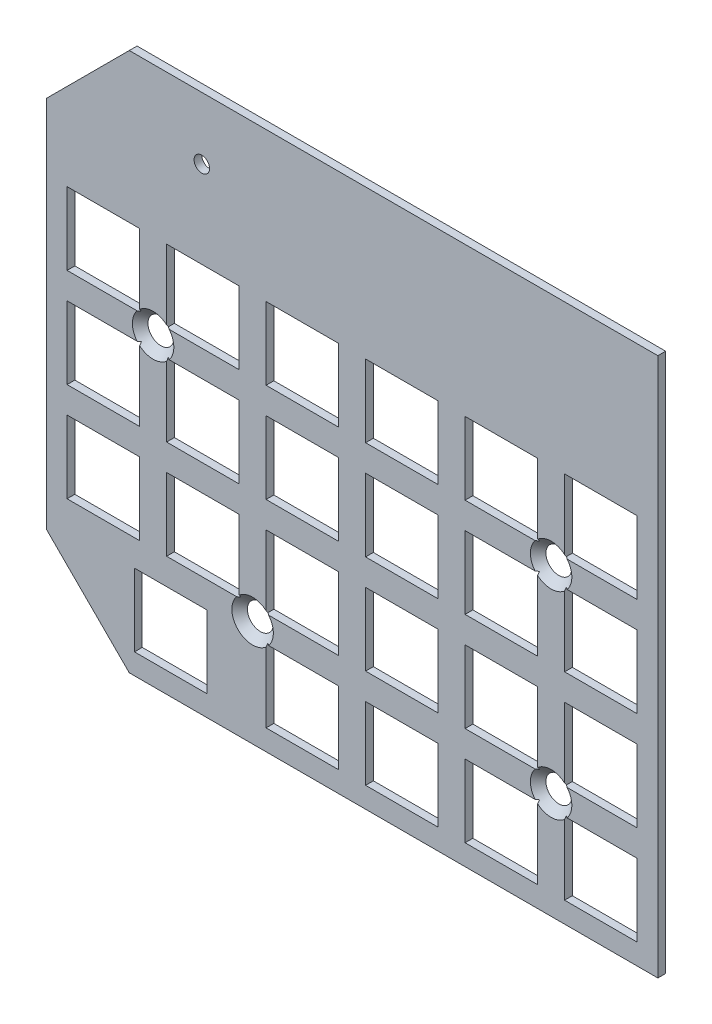
SolidWorks part; units mm, degrees
material "Alliage 1060"
ref_plane "Plan de face" through (0, 0, 0) normal (0, 0, 1) x (1, 0, 0)
ref_plane "Plan de dessus" through (0, 0, 0) normal (0, 1, 0) x (1, 0, 0)
ref_plane "Plan de droite" through (0, 0, 0) normal (1, 0, 0) x (0, 0, -1)
other "Centre de masse"
sketch "Esquisse1" plane through (0, 0, 0) normal (0, 0, 1) x (1, 0, 0)
  line L0 (0, -85) -> (16, -101)
  line L4 (118, 3) -> (118, -101)
  line L5 (16, 3) -> (0, -13)
  line L7 (118, 3) -> (16, 3)
  line L8 (0, -13) -> (0, -85)
  line L9 (16, -101) -> (118, -101)
  dimension "D1" = 104
  dimension "D2" = 118
  dimension "D3" = 16
  dimension "D4" = 16
  dimension "D5" = 16
  dimension "D6" = 16
extrude "Boss.-Extru.1" add sketch "Esquisse1" along normal blind 1.5
sketch "Esquisse2" plane through (0, 0, 1.5) normal (0, 0, 1) x (1, 0, 0)
  line L0 (0, -13) -> (0, -85) construction
  line L1 (4, -25.7494) -> (18, -25.7494)
  line L2 (4, -25.7494) -> (4, -39.7494)
  line L3 (4, -39.7494) -> (18, -39.7494)
  line L4 (18, -25.7494) -> (18, -39.7494)
  line L5 (11, -39.7494) -> (11, -25.7494) construction
  line L6 (4, -32.7494) -> (18, -32.7494) construction
  line L7 (118, 3) -> (16, 3) construction
  line L12 (23.2, -25.7494) -> (23.2, -39.7494)
  line L13 (23.2, -25.7494) -> (37.2, -25.7494)
  line L14 (37.2, -25.7494) -> (37.2, -39.7494)
  line L15 (23.2, -39.7494) -> (37.2, -39.7494)
  line L16 (42.4, -25.7494) -> (42.4, -39.7494)
  line L17 (42.4, -25.7494) -> (56.4, -25.7494)
  line L18 (56.4, -25.7494) -> (56.4, -39.7494)
  line L19 (42.4, -39.7494) -> (56.4, -39.7494)
  line L20 (61.6, -25.7494) -> (61.6, -39.7494)
  line L21 (61.6, -25.7494) -> (75.6, -25.7494)
  line L22 (75.6, -25.7494) -> (75.6, -39.7494)
  line L23 (61.6, -39.7494) -> (75.6, -39.7494)
  line L24 (80.8, -25.7494) -> (80.8, -39.7494)
  line L25 (80.8, -25.7494) -> (94.8, -25.7494)
  line L26 (94.8, -25.7494) -> (94.8, -39.7494)
  line L27 (80.8, -39.7494) -> (94.8, -39.7494)
  line L28 (100, -25.7494) -> (100, -39.7494)
  line L29 (100, -25.7494) -> (114, -25.7494)
  line L30 (114, -25.7494) -> (114, -39.7494)
  line L31 (100, -39.7494) -> (114, -39.7494)
  line L32 (23.2, -44.8329) -> (23.2, -58.8329)
  line L33 (23.2, -44.8329) -> (37.2, -44.8329)
  line L34 (37.2, -44.8329) -> (37.2, -58.8329)
  line L35 (23.2, -58.8329) -> (37.2, -58.8329)
  line L36 (42.4, -44.8329) -> (42.4, -58.8329)
  line L37 (42.4, -44.8329) -> (56.4, -44.8329)
  line L38 (56.4, -44.8329) -> (56.4, -58.8329)
  line L39 (42.4, -58.8329) -> (56.4, -58.8329)
  line L40 (61.6, -44.8329) -> (61.6, -58.8329)
  line L41 (61.6, -44.8329) -> (75.6, -44.8329)
  line L42 (75.6, -44.8329) -> (75.6, -58.8329)
  line L43 (61.6, -58.8329) -> (75.6, -58.8329)
  line L44 (80.8, -44.8329) -> (80.8, -58.8329)
  line L45 (80.8, -44.8329) -> (94.8, -44.8329)
  line L46 (94.8, -44.8329) -> (94.8, -58.8329)
  line L47 (80.8, -58.8329) -> (94.8, -58.8329)
  line L48 (100, -44.8329) -> (100, -58.8329)
  line L49 (100, -44.8329) -> (114, -44.8329)
  line L50 (114, -44.8329) -> (114, -58.8329)
  line L51 (100, -58.8329) -> (114, -58.8329)
  line L52 (23.2, -63.9165) -> (23.2, -77.9165)
  line L53 (23.2, -63.9165) -> (37.2, -63.9165)
  line L54 (37.2, -63.9165) -> (37.2, -77.9165)
  line L55 (23.2, -77.9165) -> (37.2, -77.9165)
  line L56 (42.4, -63.9165) -> (42.4, -77.9165)
  line L57 (42.4, -63.9165) -> (56.4, -63.9165)
  line L58 (56.4, -63.9165) -> (56.4, -77.9165)
  line L59 (42.4, -77.9165) -> (56.4, -77.9165)
  line L60 (61.6, -63.9165) -> (61.6, -77.9165)
  line L61 (61.6, -63.9165) -> (75.6, -63.9165)
  line L62 (75.6, -63.9165) -> (75.6, -77.9165)
  line L63 (61.6, -77.9165) -> (75.6, -77.9165)
  line L64 (80.8, -63.9165) -> (80.8, -77.9165)
  line L65 (80.8, -63.9165) -> (94.8, -63.9165)
  line L66 (94.8, -63.9165) -> (94.8, -77.9165)
  line L67 (80.8, -77.9165) -> (94.8, -77.9165)
  line L68 (100, -63.9165) -> (100, -77.9165)
  line L69 (100, -63.9165) -> (114, -63.9165)
  line L70 (114, -63.9165) -> (114, -77.9165)
  line L71 (100, -77.9165) -> (114, -77.9165)
  line L72 (4, -44.8329) -> (4, -58.8329)
  line L73 (4, -44.8329) -> (18, -44.8329)
  line L74 (18, -44.8329) -> (18, -58.8329)
  line L75 (4, -58.8329) -> (18, -58.8329)
  line L76 (4, -63.9165) -> (4, -77.9165)
  line L77 (4, -63.9165) -> (18, -63.9165)
  line L78 (18, -63.9165) -> (18, -77.9165)
  line L79 (4, -77.9165) -> (18, -77.9165)
  line L112 (42.4, -83) -> (42.4, -97)
  line L113 (42.4, -83) -> (56.4, -83)
  line L114 (56.4, -83) -> (56.4, -97)
  line L115 (42.4, -97) -> (56.4, -97)
  line L116 (61.6, -83) -> (61.6, -97)
  line L117 (61.6, -83) -> (75.6, -83)
  line L118 (75.6, -83) -> (75.6, -97)
  line L119 (61.6, -97) -> (75.6, -97)
  line L120 (80.8, -83) -> (80.8, -97)
  line L121 (80.8, -83) -> (94.8, -83)
  line L122 (94.8, -83) -> (94.8, -97)
  line L123 (80.8, -97) -> (94.8, -97)
  line L124 (100, -83) -> (100, -97)
  line L125 (100, -83) -> (114, -83)
  line L126 (114, -83) -> (114, -97)
  line L127 (100, -97) -> (114, -97)
  line L128 (4, -83) -> (4, -97) [skipped]
  line L129 (4, -83) -> (18, -83) [skipped]
  line L130 (18, -83) -> (18, -97) [skipped]
  line L131 (4, -97) -> (18, -97) [skipped]
  line L132 (23.2, -83) -> (23.2, -97) [skipped]
  line L133 (23.2, -83) -> (37.2, -83) [skipped]
  line L134 (37.2, -83) -> (37.2, -97) [skipped]
  line L135 (23.2, -97) -> (37.2, -97) [skipped]
  line L137 (17, -83) -> (31, -83)
  line L138 (17, -83) -> (17, -97)
  line L139 (17, -97) -> (31, -97)
  line L140 (31, -83) -> (31, -97)
  line L141 (24, -97) -> (24, -83) construction
  line L142 (17, -90) -> (31, -90) construction
  line L143 (16, -101) -> (118, -101) construction
  circle A8 centre (30, -9) radius 1.5
  point P0 (11, -32.7494)
  point P19 (24, -90)
  dimension "D5" = 4
  dimension "D7" = 12
  dimension "D6" = 30
  dimension "D1" = 14
  dimension "D2" = 14
  dimension "D3" = 4
  dimension "D4" = 6
  dimension "D9" = 14
  dimension "D10" = 14
  dimension "D11" = 17
  dimension "D12" = 5.2
  dimension "D8" = 4
extrude "Enlèv. mat.-Extru.1" cut sketch "Esquisse2" against normal blind 1.5
sketch "Esquisse9" plane through (0, 0, 1.5) normal (0, 0, 1) x (1, 0, 0)
  line L0 (18, -44.8329) -> (23.2, -39.7494) construction
  line L1 (94.8, -39.7494) -> (100, -44.8329) construction
  line L2 (94.8, -83) -> (100, -77.9165) construction
  line L3 (37.2, -77.9165) -> (42.4, -83) construction
  point P16 (20.6, -42.2911)
  point P17 (39.8, -80.4582)
  point P18 (97.4, -42.2911)
  point P19 (97.4, -80.4582)
hole_wizard "Fraisage pour vis à tête fraisée M42" positions "Esquisse17" profile "Esquisse18" countersink size "M4" standard "Ansi Metric" end condition through all
sketch "Esquisse17" plane through (0, 0, 1.5) normal (0, 0, 1) x (1, 0, 0)
  point P0 (20.6, -42.2911)
  point P4 (97.4, -42.2911)
  point P7 (97.4, -80.4582)
  point P10 (39.8, -80.4582)
sketch "Esquisse18" plane through (20.6, -42.2911, 1.5) normal (1, 0, 0) x (0, -1, 0)
  line L0 (0, 0) -> (0, 1.5)
  line L1 (0, 1.5) -> (2.25, 1.5)
  line L2 (2.25, 1.5) -> (2.25, 1.75)
  line L3 (2.25, 1.75) -> (4, 0)
  line L5 (4, 0) -> (0, 0)
  line L6 (-2.25, 1.75) -> (-4, 0) construction
  line L11 (0, -6.35) -> (0, 107.95) construction
  dimension "Diamètre du perçage jusqu'au prochain" = 4.5
  dimension "Profondeur du perçage jusqu'au prochain" = 1.5
  dimension "Diamètre du fraisage entrant" = 8
  dimension "Angle du fraisage entrant" = 90
